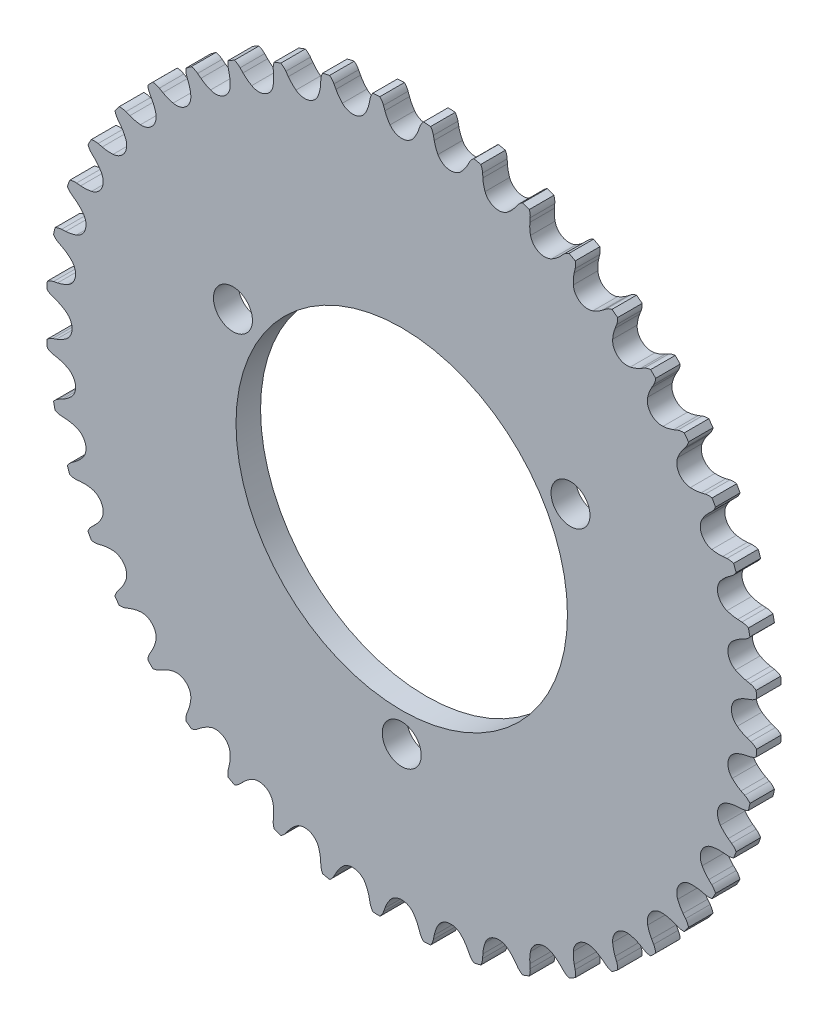
SolidWorks part; units mm, degrees
ref_plane "Plan de face" through (0, 0, 0) normal (0, 0, 1) x (1, 0, 0)
ref_plane "Plan de dessus" through (0, 0, 0) normal (0, 1, 0) x (1, 0, 0)
ref_plane "Plan de droite" through (0, 0, 0) normal (1, 0, 0) x (0, 0, -1)
sketch "Master Sk" plane through (0, 0, 0) normal (0, 0, 1) x (1, 0, 0)
  line L0 (0, 0) -> (0, 56.0702) construction
  line L1 (0, 0) -> (-7.9796, 55.4995) construction
  line L2 (0, 56.0702) -> (-7.9796, 55.4995) construction
  line L3 (0, 56.0702) -> (-2.3617, 56.0702) construction
  line L4 (0, 56.0702) -> (-1.9018, 54.6699) construction
  line L5 (0, 56.0702) -> (3.0278, 58.2995) construction
  line L6 (3.0278, 58.2995) -> (-2.7379, 56.2423) construction
  line L7 (-3.9898, 55.7848) -> (-4.1685, 58.283) construction
  line L8 (-2.7379, 56.2423) -> (-3.4821, 58.3281) construction
  line L9 (0, 56.0702) -> (-6.5632, 55.6008) construction
  line L10 (-6.5632, 55.6008) -> (-2.9669, 56.8839) construction
  line L11 (-5.2941, 56.0595) -> (-4.8543, 58.2299) construction
  line L12 (-5.2941, 56.0595) -> (-5.1588, 56.7272)
  line L13 (-2.7379, 56.2423) -> (-2.9669, 56.8839)
  circle A2 centre (0, 56.0702) radius 2.35 construction
  circle A6 centre (0, 56.0702) radius 2.3618 construction
  arc A7 (0, 53.7084) -> (-1.9018, 54.6699) centre (0, 56.0702) cw
  arc A8 (-2.7379, 56.2423) -> (-1.9018, 54.6699) centre (3.0278, 58.2995) ccw
  circle A9 centre (0, 0) radius 58.4319 construction
  circle A10 centre (-6.5632, 55.6008) radius 3.8184 construction
  circle A11 centre (0, 56.0702) radius 3.8184 construction
  arc A12 (-5.2941, 56.0595) -> (-5.8978, 54.3841) centre (-11.2939, 57.2752) cw
  arc A13 (-7.6435, 53.1617) -> (-5.8978, 54.3841) centre (-7.9796, 55.4995) ccw
  arc A14 (0, 53.7084) -> (-7.6435, 53.1617) centre (0, 0) ccw
  arc A15 (-4.1685, 58.283) -> (-2.9669, 56.8839) centre (-5.388, 56.0201) cw
  arc A16 (-4.1685, 58.283) -> (-5.1588, 56.7272) centre (-2.6393, 56.2167) ccw
  arc A17 (-9.2657, 52.9031) -> (2.9355, 53.6281) centre (0, 0) ccw construction
  arc A18 (-7.6435, 53.1617) -> (-9.2657, 52.9031) centre (0, 0) ccw construction
  arc A19 (2.9355, 53.6281) -> (0, 53.7084) centre (0, 0) ccw construction
  dimension "D3" = 4.7
  dimension "D4" = 4.7235
  dimension "D9" = 6.1217
  dimension "D1" = 8
  dimension "D2" = 8.182
  dimension "D5" = 36.364
  dimension "D6" = 3.76
  dimension "D7" = 16.727
  dimension "D8" = 6.1217
  dimension "D10" = 6.58
sketch "Esquisse2" plane through (0, 0, 0) normal (0, 0, 1) x (1, 0, 0)
  circle A1 centre (0, 0) radius 53.7084
  arc A2 (-9.2657, 52.9031) -> (2.9355, 53.6281) centre (0, 0) ccw construction
extrude "Boss.-Extru.1" add sketch "Esquisse2" along normal blind 4
sketch "Esquisse3" plane through (0, 0, 4) normal (0, 0, 1) x (1, 0, 0)
  line L2 (-5.1588, 56.7272) -> (-5.2941, 56.0595)
  line L3 (-2.7379, 56.2423) -> (-2.9669, 56.8839)
  line L4 (-5.1588, 56.7272) -> (-5.2941, 56.0595)
  line L5 (-2.7379, 56.2423) -> (-2.9669, 56.8839)
  arc A7 (-4.1685, 58.283) -> (-5.1588, 56.7272) centre (-2.6393, 56.2167) ccw
  arc A8 (-2.9669, 56.8839) -> (-4.1685, 58.283) centre (-5.388, 56.0201) ccw
  arc A9 (-2.7379, 56.2423) -> (-1.9018, 54.6699) centre (3.0278, 58.2995) ccw
  arc A10 (-1.9018, 54.6699) -> (0, 53.7084) centre (0, 56.0702) ccw
  arc A11 (0, 53.7084) -> (-7.6435, 53.1617) centre (0, 0) ccw
  arc A12 (-7.6435, 53.1617) -> (-5.8978, 54.3841) centre (-7.9796, 55.4995) ccw
  arc A13 (-5.8978, 54.3841) -> (-5.2941, 56.0595) centre (-11.2939, 57.2752) ccw
  arc A14 (-4.1685, 58.283) -> (-5.1588, 56.7272) centre (-2.6393, 56.2167) ccw
  arc A15 (-2.9669, 56.8839) -> (-4.1685, 58.283) centre (-5.388, 56.0201) ccw
  arc A16 (-2.7379, 56.2423) -> (-1.9018, 54.6699) centre (3.0278, 58.2995) ccw
  arc A17 (-1.9018, 54.6699) -> (0, 53.7084) centre (0, 56.0702) ccw
  arc A18 (0, 53.7084) -> (-7.6435, 53.1617) centre (0, 0) ccw
  arc A19 (-7.6435, 53.1617) -> (-5.8978, 54.3841) centre (-7.9796, 55.4995) ccw
  arc A20 (-5.8978, 54.3841) -> (-5.2941, 56.0595) centre (-11.2939, 57.2752) ccw
  dimension "D1" = 0
extrude "Boss.-Extru.2" add sketch "Esquisse3" against normal up to surface (4 mm away) up to face at (53.7084, 0, 0)
ref_axis "Axe1" through (0, 0, 4) along (0, 0, -1)
pattern_circular "Répétition circulaire1" count 44 over 360 about axis through (0, 0, 4) along (0, 0, -1) of "Boss.-Extru.2"
sketch "Esquisse4" plane through (0, 0, 4) normal (0, 0, 1) x (1, 0, 0)
  circle A0 centre (0, 0) radius 27
  dimension "D1" = 54
extrude "Enlèv. mat.-Extru.1" cut sketch "Esquisse4" against normal through all
hole_wizard "1/4 (0.25) Diameter Hole1" positions "Sketch3" profile "Sketch2" hole size "1/4" standard "ANSI Inch" end condition through all
sketch "Sketch3" plane through (0, 0, 4) normal (0, 0, 1) x (1, 0, 0)
  circle A0 centre (0, 0) radius 31.75
  point P5 (0, -31.75)
  point P11 (-27.4963, 15.875)
  point P12 (27.4963, 15.875)
  dimension "D1" = 63.5
  dimension "D2" = 3
sketch "Sketch2" plane through (27.4963, 15.875, 4) normal (1, 0, 0) x (0, -1, 0)
  line L0 (0, 0) -> (0, 4)
  line L1 (0, 4) -> (3.175, 4)
  line L2 (3.175, 4) -> (3.175, 0)
  line L5 (3.175, 0) -> (0, 0)
  line L11 (0, -6.35) -> (0, 107.95) construction
  dimension "Thru Hole Dia." = 6.35
  dimension "Thru Hole Depth" = 4
sketch "Esquisse5" plane through (0, 0, 0) normal (0, 0, -1) x (-1, 0, 0)
  line L0 (0, 0) -> (0, 64.8709) construction
  line L1 (0, 0) -> (58.7515, 58.7515) construction
  line L2 (6, 41.5692) -> (6, 58.983)
  line L3 (41.5692, 6) -> (58.983, 6)
  arc A0 (9.7209, 36.7356) -> (36.7356, 9.7209) centre (0, 0) cw
  arc A1 (11.9167, 63.8983) -> (63.8983, 11.9167) centre (0, 0) cw
  arc A2 (41.5692, 6) -> (36.7356, 9.7209) centre (41.5692, 11) cw
  arc A3 (0, 65) -> (6, 64.7225) centre (0, 0) cw construction
  arc A4 (0, 65) -> (45.9619, 45.9619) centre (0, 0) cw construction
  arc A5 (0, 38) -> (6, 37.5233) centre (0, 0) cw construction
  arc A6 (0, 38) -> (26.8701, 26.8701) centre (0, 0) cw construction
  arc A7 (58.983, 6) -> (63.8983, 11.9167) centre (58.983, 11) ccw
  arc A8 (6, 58.983) -> (11.9167, 63.8983) centre (11, 58.983) cw
  arc A9 (6, 41.5692) -> (9.7209, 36.7356) centre (11, 41.5692) ccw
  point P15 (37.5233, 6)
  point P18 (64.7225, 6)
  dimension "D2" = 38
  dimension "D5" = 5
  dimension "D1" = 45
  dimension "D4" = 12
  dimension "D3" = 27
sketch "Esquisse6" plane through (0, 0, 0) normal (0, 0, -1) x (-1, 0, 0)
  circle A0 centre (0, 0) radius 57.9319
  circle A1 centre (0, 0) radius 58.4319
  dimension "D1" = 0.5
extrude "Enlèv. mat.-Extru.3" cut sketch "Esquisse6" against normal through all
equation "\"pitch\"= 8'Pas"
equation "\"Z\"= 44'Nb de dents"
equation "\"Roller\"= 4.7'Roller diam"
equation "\"D1@Master Sk\" = \"pitch\""
equation "\"D2@Master Sk\" = 360 / \"Z\""
equation "\"D3@Master Sk\" = \"Roller\""
equation "\"HubSeat\"= 1.005 * \"Roller\"'HubSeat"
equation "\"D4@Master Sk\" = \"HubSeat\""
equation "\"A\"= 35 + ( 60 / \"Z\" )'Cote A"
equation "\"D5@Master Sk\" = \"A\""
equation "\"R1\"= \"HubSeat\" / 2'Demi HubSeat"
equation "\"oc\"= \"Roller\" * 0.8'ref oc"
equation "\"D6@Master Sk\" = \"oc\""
equation "\"R2\"= 18 - ( 56 / \"Z\" )'ref r2"
equation "\"D7@Master Sk\" = \"R2\""
equation "\"D8@Master Sk\" = \"R1\" + \"oc\""
equation "\"D10@Master Sk\" = \"Roller\" * 1.4"
equation "\"R2_2\"= \"R1\" + \"oc\""
equation "\"D9@Master Sk\" = \"R2_2\""
equation "\"Ep\"= 4'épaisseur pignon"
equation "\"D1@Boss.-Extru.1\"=\"Ep\""
equation "\"D1@Répétition circulaire1\"=\"Z\""
